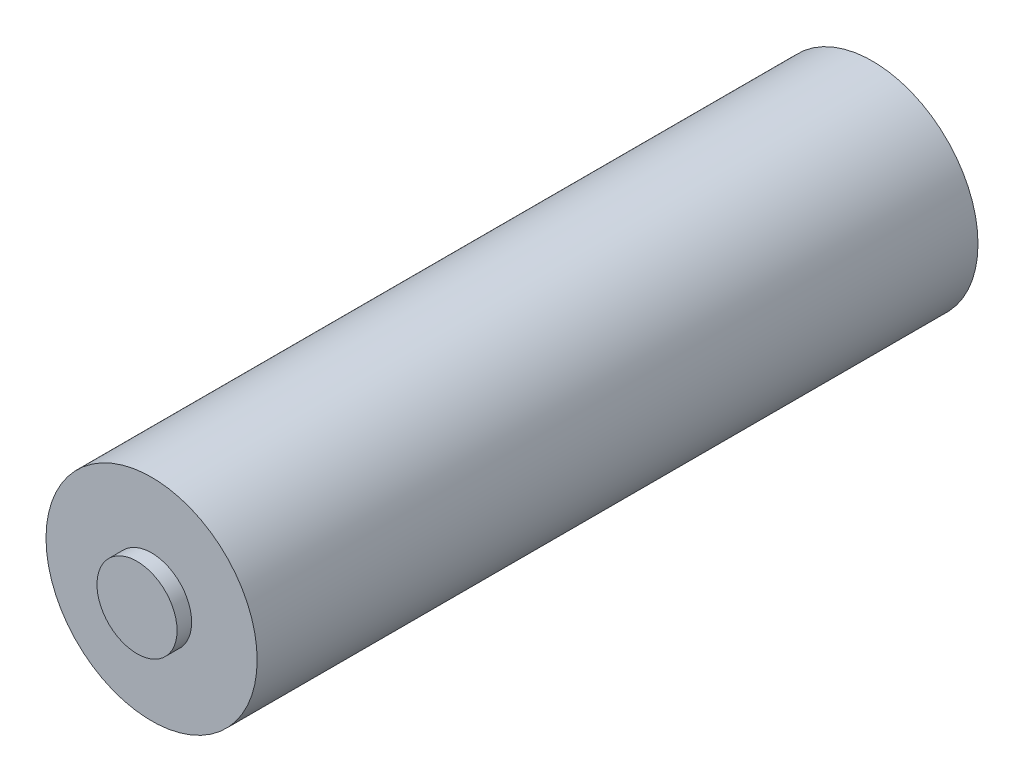
SolidWorks part; units mm, degrees
ref_plane "Front Plane" through (0, 0, 0) normal (0, 0, 1) x (1, 0, 0)
ref_plane "Top Plane" through (0, 0, 0) normal (0, 1, 0) x (1, 0, 0)
ref_plane "Right Plane" through (0, 0, 0) normal (1, 0, 0) x (0, 0, -1)
sketch "Sketch1" plane through (0, 0, 0) normal (0, 0, 1) x (1, 0, 0)
  circle A0 centre (0, 0) radius 7.25
  circle A1 centre (0, 0) radius 2.75
  dimension "D1" = 14.5
  dimension "D2" = 5.5
extrude "Boss-Extrude1" add sketch "Sketch1" along normal blind 49.5
extrude "Boss-Extrude2" add sketch "Sketch1<2>" along normal blind 50.5 contours A1 region at (0, 0, 0)
sketch "Sketch1<2>" plane through (0, 0, 0) normal (0, 0, 1) x (1, 0, 0) same geometry as "Sketch1"
